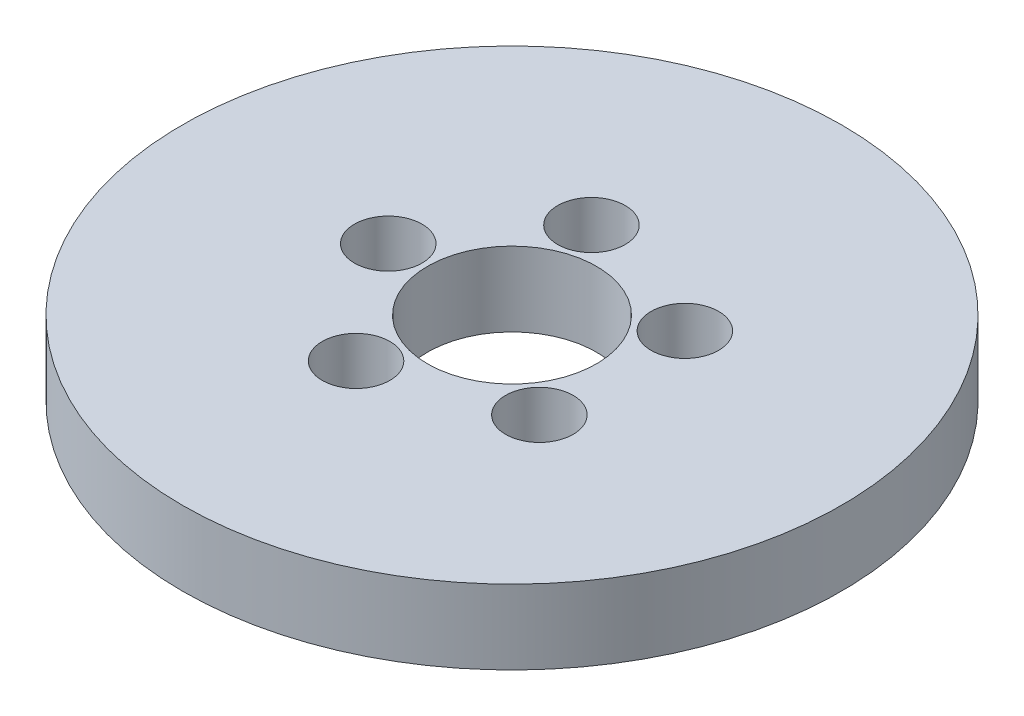
SolidWorks part; units mm, degrees
ref_plane "Front Plane" through (0, 0, 0) normal (0, 0, 1) x (1, 0, 0)
ref_plane "Top Plane" through (0, 0, 0) normal (0, 1, 0) x (1, 0, 0)
ref_plane "Right Plane" through (0, 0, 0) normal (1, 0, 0) x (0, 0, -1)
sketch "Sketch1" plane through (0, 0, 0) normal (0, 1, 0) x (1, 0, 0)
  circle A0 centre (0, 0) radius 97.5
  dimension "FLANGE_OD" = 195
extrude "Boss-Extrude1" add sketch "Sketch1" along normal blind 22
sketch "Sketch2" plane through (0, 0, 0) normal (0, 1, 0) x (1, 0, 0)
  circle A0 centre (0, 0) radius 25
  dimension "BORE_D" = 50
extrude "Cut-Extrude1" cut sketch "Sketch2" along normal through all
sketch "Sketch3" plane through (0, 22, 0) normal (0, 1, 0) x (1, 0, 0)
  circle A0 centre (0, 0) radius 36.6145 construction
  circle A1 centre (-36.6145, 0) radius 10
  dimension "BOLT_D" = 20
  dimension "BOLT_PCD" = 73.2291
extrude "Cut-Extrude2" cut sketch "Sketch3" against normal blind 16.2701
pattern_circular "CirPattern1" count 5 over 360 about axis through (0, 0, 0) along (0, 1, 0) of "Cut-Extrude2"
